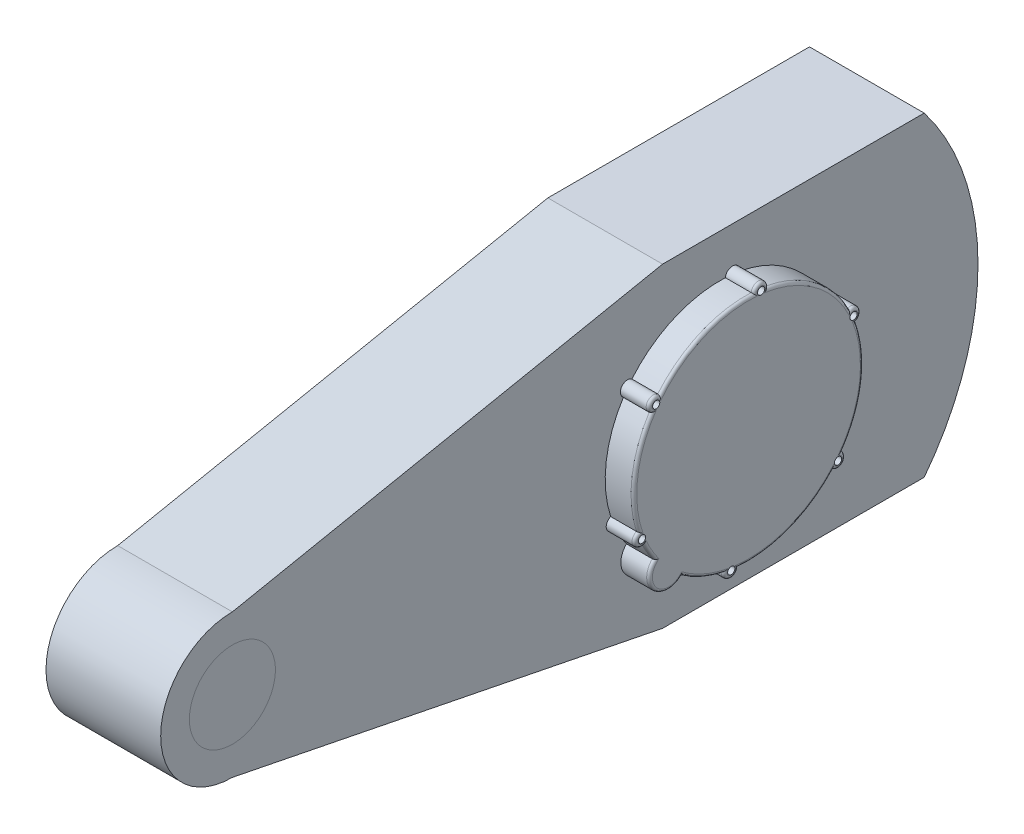
SolidWorks part; units mm, degrees
ref_plane "Alzado" through (0, 0, 0) normal (0, 0, 1) x (1, 0, 0)
ref_plane "Planta" through (0, 0, 0) normal (0, 1, 0) x (1, 0, 0)
ref_plane "Vista lateral" through (0, 0, 0) normal (1, 0, 0) x (0, 0, -1)
sketch "Croquis2" plane through (0, 0, 0) normal (1, 0, 0) x (0, 0, -1)
  line L0 (-198.0034, 0) -> (190.6058, 0) construction
  line L1 (0, 0) -> (-114.8403, -114.8403) construction
  line L2 (0, 0) -> (-140.7992, -58.321) construction
  arc A0 (-92.1638, -42.7596) -> (-82.7763, -58.9122) centre (0, 0) ccw
  arc A1 (-96.7775, -30.9302) -> (-92.1638, -42.7596) centre (-94.3474, -36.7969) ccw
  arc A2 (-82.7763, -58.9122) -> (-58.9122, -82.7763) centre (-70.8442, -70.8442) ccw
  arc A3 (-77.9564, 65.1564) -> (-85.4745, 54.9242) centre (-81.8222, 60.1187) ccw
  arc A4 (17.4489, 100.0904) -> (4.8285, 101.4852) centre (11.1532, 100.9194) ccw
  arc A5 (95.4053, 34.9341) -> (90.303, 46.561) centre (92.9754, 40.8007) ccw
  arc A6 (75.1751, -68.3466) -> (83.1128, -58.4364) centre (79.2473, -63.4743) ccw
  arc A7 (-21.6024, -99.2769) -> (-9.051, -101.196) centre (-15.3467, -100.3673) ccw
  arc A8 (-58.9122, -82.7763) -> (-21.6024, -99.2769) centre (0, 0) ccw
  arc A9 (-9.051, -101.196) -> (75.1751, -68.3466) centre (0, 0) ccw
  arc A10 (83.1128, -58.4364) -> (95.4053, 34.9341) centre (0, 0) ccw
  arc A11 (90.303, 46.561) -> (17.4489, 100.0904) centre (0, 0) ccw
  arc A12 (4.8285, 101.4852) -> (-77.9564, 65.1564) centre (0, 0) ccw
  arc A13 (-85.4745, 54.9242) -> (-96.7775, -30.9302) centre (0, 0) ccw
  point P22 (0, 0)
  dimension "D1" = 203.2
  dimension "D3" = 6.35
  dimension "D2" = 45
  dimension "D4" = 22.5
extrude "Saliente-Extruir1" add sketch "Croquis2" along normal blind 25.4
sketch "Croquis3" plane through (25.4, 0, 0) normal (1, 0, 0) x (0, 0, -1)
  circle A0 centre (-81.8222, 60.1187) radius 3.175
  circle A1 centre (-94.3474, -36.7969) radius 3.175
  circle A2 centre (-15.3467, -100.3673) radius 3.175
  circle A3 centre (79.2473, -63.4743) radius 3.175
  circle A4 centre (92.9754, 40.8007) radius 3.175
  circle A5 centre (11.1532, 100.9194) radius 3.175
  dimension "D1" = 6.35
extrude "Cortar-Extruir1" cut sketch "Croquis3" against normal through all
fillet "Redondeo2" radius 2.54 14 edges at (25.4, -51.0522, 87.8421) (25.4, -92.9185, 41.094) (25.4, -106.6444, 16.3065) (25.4, -94.6556, -36.9171) (25.4, -67.444, -84.2035) (25.4, -13.2615, -100.7308) (25.4, 43.3524, -98.7901) (25.4, 81.8755, -60.1578) (25.4, 107.231, -11.8507) (25.4, 93.036, 40.8273) (25.4, 63.8785, 86.9394) (25.4, 13.2615, 100.7308) (25.4, -82.7763, 82.7763) (25.4, -39.1042, 100.2634)
sketch "Croquis4" plane through (0, 0, 0) normal (-1, 0, 0) x (0, 0, 1)
  line L0 (0, -139.7) -> (0, 139.7) construction
  line L1 (0, 139.7) -> (-180.9471, 139.7)
  line L2 (0, -139.7) -> (-180.9471, -139.7)
  line L3 (0, 139.7) -> (50.8, 139.7)
  line L4 (0, -139.7) -> (50.8, -139.7)
  line L5 (0, 0) -> (431.8, 0) construction
  line L6 (50.8, 139.7) -> (431.8, 63.5)
  line L7 (50.8, -139.7) -> (431.8, -63.5)
  arc A0 (-180.9471, 139.7) -> (-180.9471, -139.7) centre (0, 0) ccw
  arc A1 (431.8, -63.5) -> (431.8, 63.5) centre (431.8, 0) ccw
  dimension "D1" = 457.2
  dimension "D5" = 127
  dimension "D2" = 279.4
  dimension "D3" = 50.8
  dimension "D4" = 431.8
extrude "Saliente-Extruir2" add sketch "Croquis4" along normal blind 101.6
sketch "Croquis6" plane through (0, 0, 0) normal (1, 0, 0) x (0, 0, -1)
  circle A0 centre (-431.8, 0) radius 38.1
  dimension "D1" = 76.2
split line "Línea de partición2"
sketch "草图1" plane through (-101.6, 0, 0) normal (-1, 0, 0) x (0, 0, 1)
  line L0 (-154.5452, 22.075) -> (349.198, 22.075) construction
  text T0 "HIT" font "Century Schoolbook" height 50.8
extrude "切除-拉伸1" cut sketch "草图1" against normal blind 2.54
